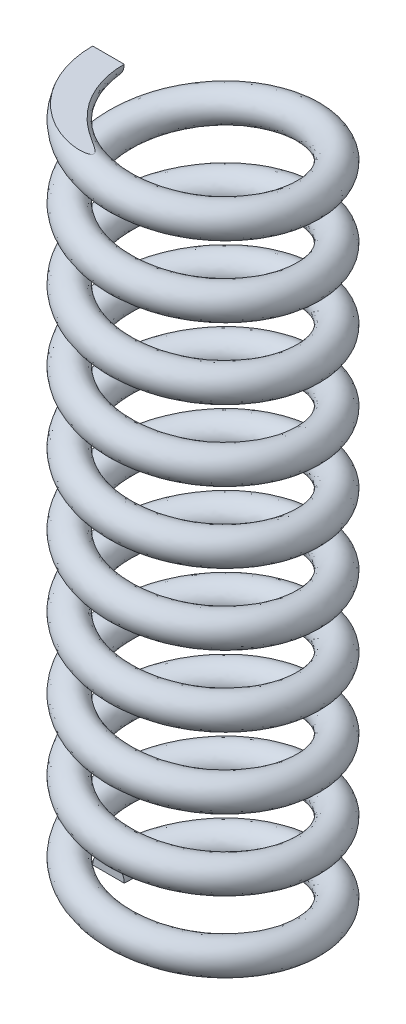
SolidWorks part; units mm, degrees
note: The reader was unsure of these and kept them because the rebuilt part matched: shared geometry of "Sketch1<2>".
ref_plane "Front Plane" through (0, 0, 0) normal (0, 0, 1) x (1, 0, 0)
ref_plane "Top Plane" through (0, 0, 0) normal (0, 1, 0) x (1, 0, 0)
ref_plane "Right Plane" through (0, 0, 0) normal (1, 0, 0) x (0, 0, -1)
sketch "Sketch1" plane through (0, 0, 0) normal (0, 1, 0) x (1, 0, 0)
  circle A0 centre (0, 0) radius 2.4
  dimension "D1" = 4.8
curve "Helix/Spiral1" pitch 1.8 height 18 turns 10
sketch "Sketch2" plane through (0, 0, 0) normal (0, 0, 1) x (1, 0, 0)
  circle A0 centre (-2.4, 0) radius 0.4
  dimension "D1" = 0.8
sweep "Sweep1" add profiles "Sketch2" path "Helix/Spiral1"
surface "Surface-Extrude1" sketch "Sketch1<2>" parameters "D1"=0.2
sketch "Sketch1<2>" plane through (0, 0, 0) normal (0, 1, 0) x (1, 0, 0) same geometry as "Sketch1"
sketch "Sketch3" plane through (0, 0, 0) normal (1, 0, 0) x (0, 0, -1)
  line L0 (3.08, 0) -> (-3.08, 0) construction
  line L1 (-5.3, 18) -> (5.3, 18)
  line L2 (-5.3, 18) -> (-5.3, 0)
  line L3 (-5.3, 0) -> (5.3, 0)
  line L4 (5.3, 18) -> (5.3, 0)
  line L5 (-5.3, 18) -> (5.3, 0) construction
  line L6 (-5.3, 0) -> (5.3, 18) construction
  line L7 (0, 3.08) -> (0, -3.08) construction
  point P0 (0, 9)
  dimension "D1" = 18
  dimension "D2" = 10.6
extrude "Cut-Extrude1" cut sketch "Sketch3" against normal through all both and the other way through all flip side to cut
equation "\"d\"= 4.8"
equation "\"b\"= 0.8"
equation "\"L\"= 18"
equation "\"D1@Sketch2\"=\"b\""
equation "\"D1@Sketch1\"=\"d\""
equation "\"D3@Helix/Spiral1\" = \"L\""
equation "\"D1@Sketch3\"=\"L\""
equation "\"D2@Sketch3\"=\"d\" + \"b\" + 5"
